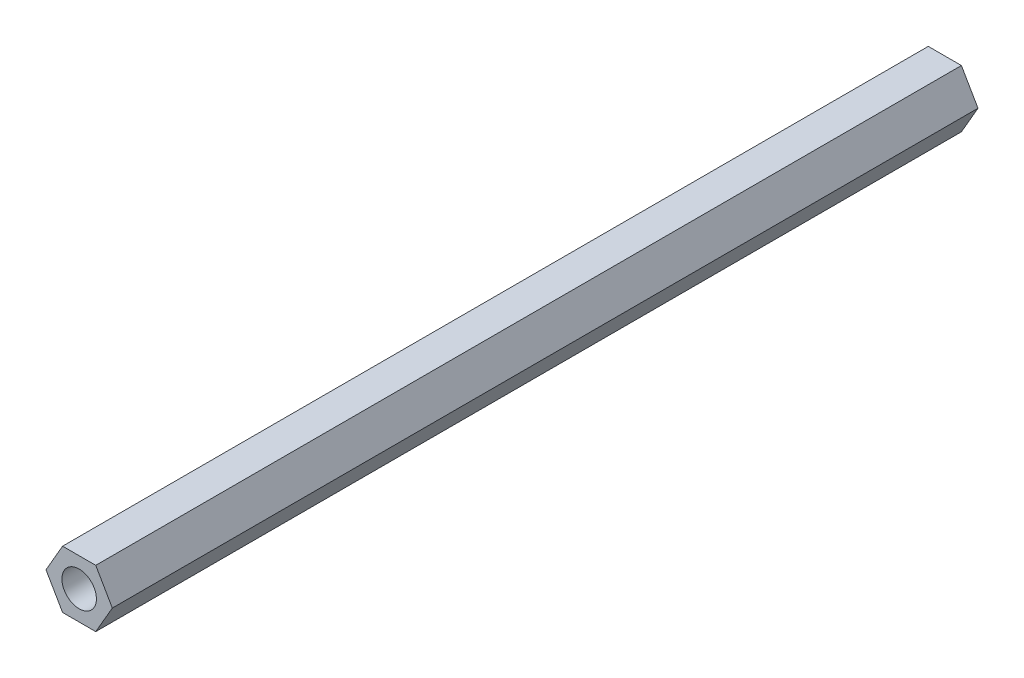
SolidWorks part; units mm, degrees
ref_plane "Alzado" through (0, 0, 0) normal (0, 0, 1) x (1, 0, 0)
ref_plane "Planta" through (0, 0, 0) normal (0, 1, 0) x (1, 0, 0)
ref_plane "Vista lateral" through (0, 0, 0) normal (1, 0, 0) x (0, 0, -1)
sketch "Croquis1" plane through (0, 0, 0) normal (0, 0, 1) x (1, 0, 0)
  line L1 (2.8868, 0) -> (1.4434, 2.5)
  line L2 (1.4434, 2.5) -> (-1.4434, 2.5)
  line L3 (-1.4434, 2.5) -> (-2.8868, 0)
  line L4 (-2.8868, 0) -> (-1.4434, -2.5)
  line L5 (-1.4434, -2.5) -> (1.4434, -2.5)
  line L6 (1.4434, -2.5) -> (2.8868, 0)
  circle A0 centre (0, 0) radius 1.5
  circle A1 centre (0, 0) radius 2.5 construction
  dimension "D1" = 3
  dimension "D2" = 5
extrude "Saliente-Extruir1" add sketch "Croquis1" against normal blind 75.36
